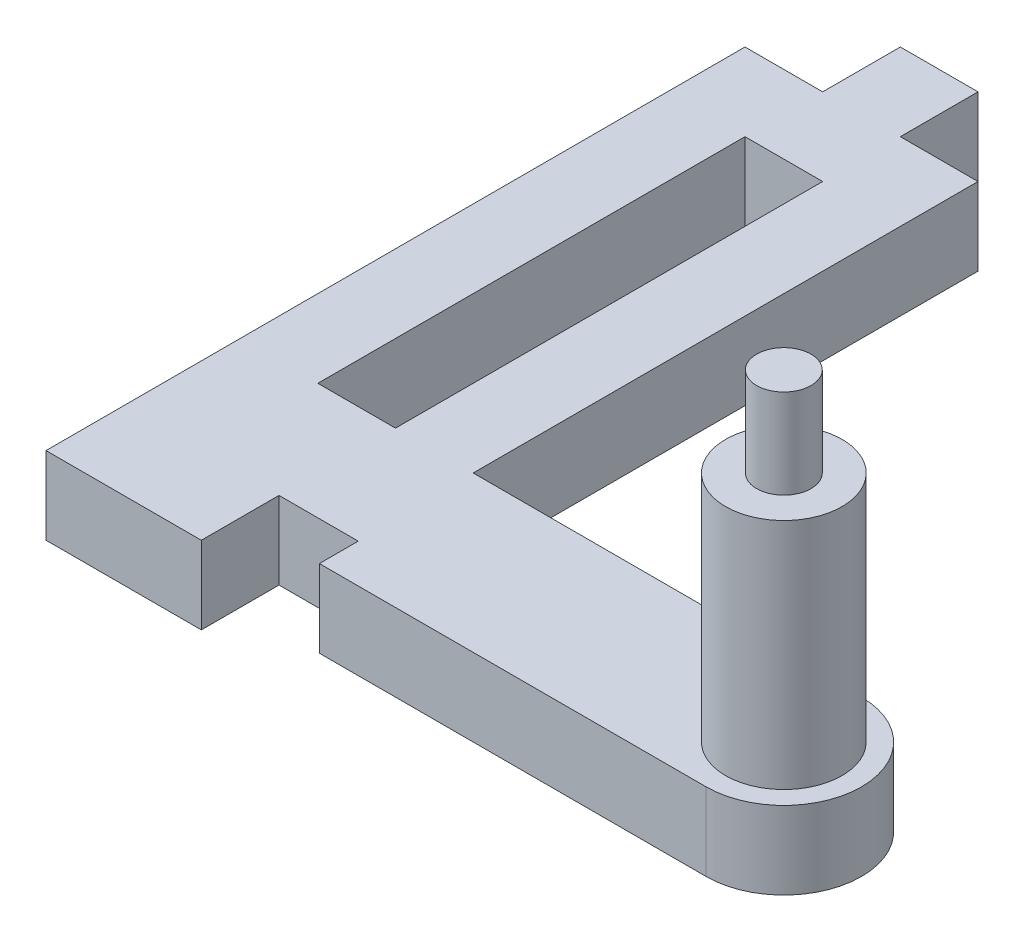
SolidWorks part; units mm, degrees
ref_plane "Front Plane" through (0, 0, 0) normal (0, 0, 1) x (1, 0, 0)
ref_plane "Top Plane" through (0, 0, 0) normal (0, 1, 0) x (1, 0, 0)
ref_plane "Right Plane" through (0, 0, 0) normal (1, 0, 0) x (0, 0, -1)
sketch "Sketch1" plane through (0, 0, 0) normal (0, 1, 0) x (1, 0, 0)
  line L1 (0, 0) -> (45, 0)
  line L2 (0, 0) -> (0, 12)
  line L3 (0, 12) -> (45, 12)
  line L5 (0, 0) -> (15, 0)
  line L6 (0, 0) -> (0, -5)
  line L7 (0, -5) -> (15, -5)
  line L8 (15, 0) -> (15, -5)
  line L9 (0, 12) -> (24, 12)
  line L10 (0, 12) -> (0, 55.0692)
  line L11 (0, 55.0692) -> (24, 55.0692)
  line L12 (24, 12) -> (24, 55.0692)
  circle A0 centre (45, 6) radius 3
  arc A1 (45, 0) -> (45, 12) centre (45, 6) ccw
  circle A6 centre (12, 53.0692) radius 0.7
  circle A7 centre (21.5263, 36.5692) radius 0.7
  circle A8 centre (2.4737, 36.5692) radius 0.7
  circle A11 centre (12, 42.0692) radius 2
  dimension "D4" = 45
  dimension "D3" = 6
  dimension "D11" = 1.4
  dimension "D1" = 5
  dimension "D2" = 15
  dimension "D5" = 6
  dimension "D13" = 3
sketch "Sketch2" plane through (0, 0, 0) normal (0, 1, 0) x (1, 0, 0)
  line L0 (13.8867, 45.212) -> (13.8867, 40)
  line L1 (0, 0) -> (15, 0)
  line L5 (0, 0) -> (15.1, 0)
  line L6 (0, 0) -> (0, 40)
  line L7 (0, 40) -> (15, 40)
  line L8 (15, 7.5) -> (15, 40)
  line L9 (10, 40) -> (5, 40)
  line L10 (10, 40) -> (10, 45)
  line L11 (10, 45) -> (5, 45)
  line L12 (5, 40) -> (5, 45)
  line L17 (13.3723, 20.2678) -> (35.2318, 32.8884)
  line L18 (35.2318, 32.8884) -> (15, 21.2076)
  line L19 (28.1168, 45.212) -> (36.8437, 51.9084) construction
  line L20 (15, 7.5) -> (40, 7.5)
  line L21 (15.1, 0) -> (15.1, -2.5)
  line L22 (15.1, -2.5) -> (40, -2.5)
  line L24 (15, 7.5) -> (0, 7.5)
  line L25 (5, 35) -> (10, 35)
  line L26 (5, 35) -> (5, 5)
  line L27 (5, 5) -> (10, 5)
  line L28 (10, 35) -> (10, 5)
  line L30 (0, 0) -> (10, 0)
  line L31 (0, 0) -> (0, -5)
  line L32 (0, -5) -> (10, -5)
  line L33 (10, 0) -> (10, -5)
  circle A10 centre (28.1168, 45.212) radius 14.2301
  circle A11 centre (28.1168, 45.212) radius 2
  circle A12 centre (40, 2.5) radius 39.7 construction
  circle A13 centre (28.1168, 45.212) radius 4.6343 construction
  arc A14 (40, -2.5) -> (40, 7.5) centre (40, 2.5) ccw
  circle A15 centre (36.8437, 51.9084) radius 0.7
  circle A16 centre (38.7225, 39.6004) radius 0.7
  circle A17 centre (27.124, 44.1273) radius 0.7
  dimension "D5" = 79.4
  dimension "D6" = 40
  dimension "D7" = 5
  dimension "D8" = 2.5
  dimension "D9" = 60
  dimension "D10" = 5
  dimension "D14" = 52.5
  dimension "D1" = 40
  dimension "D2" = 5
  dimension "D3" = 5
  dimension "D4" = 5
  dimension "D11" = 5
  dimension "D12" = 11
  dimension "D13" = 10
  dimension "D16" = 5
  dimension "D17" = 5
  dimension "D18" = 5
  dimension "D19" = 5
  dimension "D20" = 5.1
  dimension "D21" = 5
  dimension "D15" = 3
extrude "Boss-Extrude1" add sketch "Sketch2" along normal blind 5 contours L22 A14 L20 L24 L28 L27 L26 L6 L1 L5 L21 | L28 L24 L26 L27 | L1 | L5 L21 L22 A14 L20 L8 L7 L6 | L10 L9 L12 L11 | L26 L25 L28 L27 region at (23.8429, 0, -2.7434) region at (7.5, 0, -6.25) region at (5, 0, 2.5)
sketch "Sketch3" plane through (0, 5, 0) normal (0, 1, 0) x (1, 0, 0)
  circle A0 centre (40, 2.5) radius 3.75
extrude "Boss-Extrude2" add sketch "Sketch3" along normal blind 15
sketch "Sketch4" plane through (0, 20, 0) normal (0, 1, 0) x (1, 0, 0)
  circle A0 centre (40, 2.5) radius 3
  circle A1 centre (40, 2.5) radius 1.75
extrude "Boss-Extrude3" add sketch "Sketch4" along normal blind 5.75 contours A1
